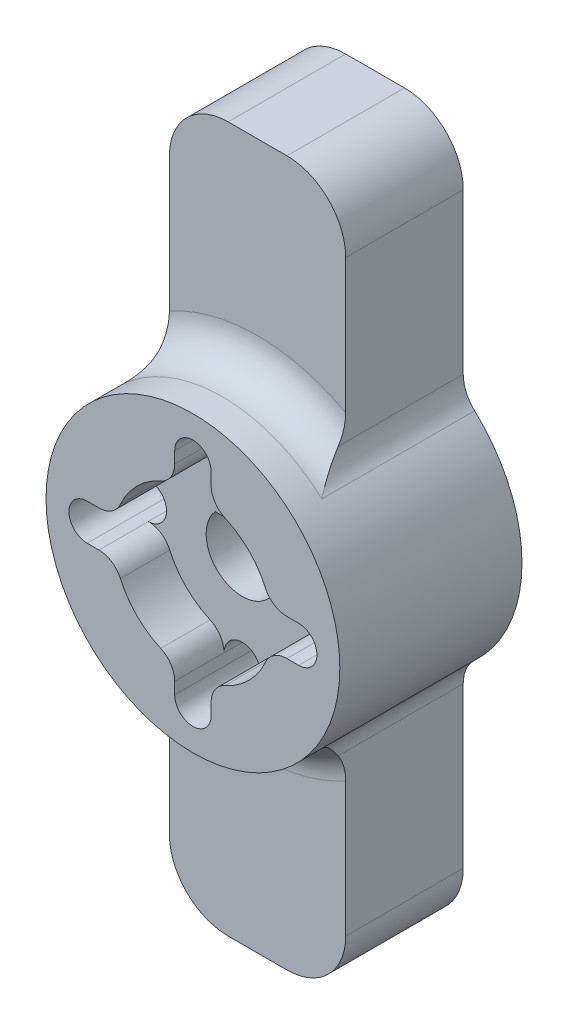
SolidWorks part; units mm, degrees
ref_plane "Plano frontal" through (0, 0, 0) normal (0, 0, 1) x (1, 0, 0)
ref_plane "Plano superior" through (0, 0, 0) normal (0, 1, 0) x (1, 0, 0)
ref_plane "Plano direito" through (0, 0, 0) normal (1, 0, 0) x (0, 0, -1)
sketch "Esboço1" plane through (0, 0, 0) normal (0, 0, 1) x (1, 0, 0)
  circle A0 centre (0, 0) radius 12.5
  dimension "D1" = 25
extrude "Ressalto-extrusão1" add sketch "Esboço1" along normal blind 11.3
sketch "Esboço2" plane through (0, 0, 11.3) normal (0, 0, 1) x (1, 0, 0)
  circle A0 centre (0, 0) radius 6.75
  circle A1 centre (0, 0) radius 12.5
  circle A2 centre (0, 0) radius 12.5
  dimension "D2" = 13.5
  dimension "D1" = 0
extrude "Ressalto-extrusão2" add sketch "Esboço2" along normal blind 4.2
sketch "Esboço3" plane through (0, 0, 11.3) normal (0, 0, 1) x (1, 0, 0)
  line L0 (-2.3141, 2.025) -> (2.3141, 2.025)
  line L1 (0, -3.075) -> (0, 2.025) construction
  arc A0 (-2.3141, 2.025) -> (2.3141, 2.025) centre (0, 0) ccw
  dimension "D1" = 6.15
  dimension "D2" = 5.1
extrude "Corte-extrusão1" cut sketch "Esboço3" against normal through all
sketch "Esboço5" plane through (0, 0, 0) normal (0, 0, -1) x (-1, 0, 0)
  line L0 (0, 0) -> (0, 8.5) construction
  line L1 (0, 9) -> (0, 8) construction
  line L2 (1.55, 9) -> (1.55, 8)
  line L3 (-1.55, 9) -> (-1.55, 8)
  line L4 (-9, -1.55) -> (-8, -1.55)
  line L5 (-9, 1.55) -> (-8, 1.55)
  line L6 (-9, 0) -> (-8, 0) construction
  line L7 (1.55, -9) -> (1.55, -8)
  line L8 (-1.55, -9) -> (-1.55, -8)
  line L9 (0, -9) -> (0, -8) construction
  line L10 (9, 1.55) -> (8, 1.55)
  line L11 (9, -1.55) -> (8, -1.55)
  line L12 (9, 0) -> (8, 0) construction
  arc A0 (1.55, 9) -> (-1.55, 9) centre (0, 9) ccw
  arc A1 (-1.55, 8) -> (1.55, 8) centre (0, 8) ccw
  arc A2 (-9, 1.55) -> (-9, -1.55) centre (-9, 0) ccw
  arc A3 (-8, -1.55) -> (-8, 1.55) centre (-8, 0) ccw
  arc A4 (-1.55, -9) -> (1.55, -9) centre (0, -9) ccw
  arc A5 (1.55, -8) -> (-1.55, -8) centre (0, -8) ccw
  arc A6 (9, -1.55) -> (9, 1.55) centre (9, 0) ccw
  arc A7 (8, 1.55) -> (8, -1.55) centre (8, 0) ccw
  point P5 (0, 8.5)
  point P15 (-8.5, 0)
  point P22 (0, -8.5)
  point P29 (8.5, 0)
  point P34 (0, 0)
  dimension "D2" = 1.55
  dimension "D1" = 8.5
  dimension "D3" = 1
  dimension "D4" = 4
extrude "Corte-extrusão2" cut sketch "Esboço5" against normal through all
sketch "Esboço6" plane through (0, 0, 11.3) normal (0, 0, 1) x (1, 0, 0)
  line L0 (1.55, 9) -> (1.55, 8) construction
  line L1 (-1.55, 8) -> (-1.55, 9) construction
  line L2 (1.55, 9) -> (1.55, 8)
  line L3 (-1.55, 8) -> (-1.55, 9)
  line L4 (-1.55, 8) -> (-1.55, 6.45)
  line L5 (-1.55, 6.45) -> (1.55, 6.45)
  line L6 (1.55, 6.45) -> (1.55, 8)
  line L7 (-1.55, 9) -> (1.55, 9)
  arc A2 (-0.8402, 6.6975) -> (0.8402, 6.6975) centre (0, 8) ccw construction
extrude "Corte-extrusão3" cut sketch "Esboço6" along normal through all
pattern_circular "PadrãoCircular1" count 4 over 360 about axis through (0, 0, 0) along (0, 0, 1) of "Corte-extrusão3"
fillet "Filete2" radius 2 8 edges at (-6.5696, 1.55, 13.4) (-6.5696, -1.55, 13.4) (-1.55, -6.5696, 13.4) (1.55, -6.5696, 13.4) (6.5696, -1.55, 13.4) (6.5696, 1.55, 13.4) (1.55, 6.5696, 13.4) (-1.55, 6.5696, 13.4)
sketch "Esboço7" plane through (0, 0, 0) normal (0, 0, -1) x (-1, 0, 0)
  line L0 (0, 0) -> (0, 30)
  line L1 (-7.5, -30) -> (-7.5, -10)
  line L2 (-7.5, -30) -> (7.5, -30)
  line L3 (-7.5, 30) -> (7.5, 30)
  line L4 (7.5, -30) -> (7.5, -10)
  line L5 (-7.5, -30) -> (7.5, 30) construction
  line L6 (-7.5, 30) -> (7.5, -30) construction
  line L7 (-7.5, 10) -> (-7.5, 30)
  line L8 (7.5, 10) -> (7.5, 30)
  circle A0 centre (0, 0) radius 12.5 construction
  arc A1 (7.5, 10) -> (-7.5, 10) centre (0, 0) ccw
  arc A2 (-7.5, -10) -> (7.5, -10) centre (0, 0) ccw
  circle M23 centre (0, 0) radius 12.5
  dimension "D1" = 30
  dimension "D2" = 15
extrude "Ressalto-extrusão3" add sketch "Esboço7" against normal blind 10 contours L2 L4 L1 M23 | L8 L3 L0 M23 | L7 L0 L3 M23 region at (3.8334, 20.8369, 0) region at (-3.8334, 20.8369, 0) region at (0, -20.8369, 0)
fillet "Filete3" radius 5 4 edges at (7.5, -30, 5) (-7.5, -30, 5) (7.5, 30, 5) (-7.5, 30, 5)
fillet "Filete4" radius 3 2 edges at (0, 12.5, 10) (0, -12.5, 10)
fillet "Filete5" radius 3 4 edges at (7.5, -10, 6.5) (7.5, 10, 6.5) (-7.5, 10, 6.5) (-7.5, -10, 6.5)
